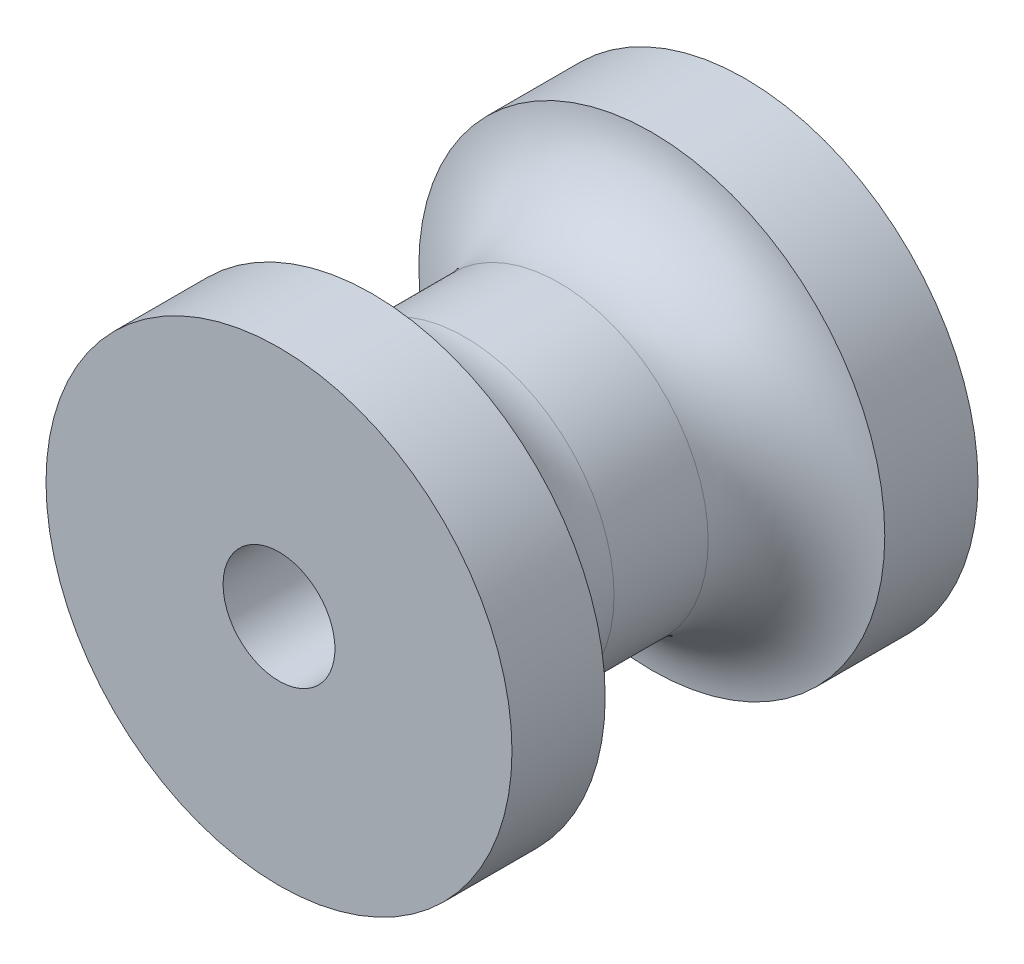
SolidWorks part; units mm, degrees
ref_plane "Front Plane" through (0, 0, 0) normal (1, 0, 0) x (0, 1, 0)
ref_plane "Top Plane" through (0, 0, 0) normal (0, 0, 1) x (0, 1, 0)
ref_plane "Right Plane" through (0, 0, 0) normal (0, 1, 0) x (-1, 0, 0)
sketch "Sketch2" plane through (0, 0, 0) normal (1, 0, 0) x (0, 1, 0)
  line L0 (0, 0) -> (0, 6.35) construction
  line L1 (0, 0) -> (6.35, 0) construction
  line L2 (6.35, 0) -> (1.524, 0)
  line L3 (6.35, 0) -> (6.35, 2.54)
  line L4 (0, 6.35) -> (6.35, 6.35) construction
  line L5 (6.35, 6.35) -> (6.35, 0) construction
  line L6 (6.35, 2.54) -> (4.064, 2.54)
  line L7 (4.064, 2.54) -> (4.064, 10.16)
  line L8 (1.524, 0) -> (1.524, 12.7)
  line L9 (1.524, 6.35) -> (4.064, 6.35) construction
  line L10 (6.35, 12.7) -> (1.524, 12.7)
  line L11 (6.35, 12.7) -> (6.35, 10.16)
  line L12 (6.35, 10.16) -> (4.064, 10.16)
  dimension "D1" = 1.524
  dimension "D2" = 6.35
  dimension "D3" = 6.35
  dimension "D4" = 2.54
  dimension "D5" = 2.54
revolve "Revolve1" add sketch "Sketch2" angle 360 about L0
fillet "Fillet1" radius 2.54 2 edges at (-4.064, 0, 2.54) (-4.064, 0, 10.16)
